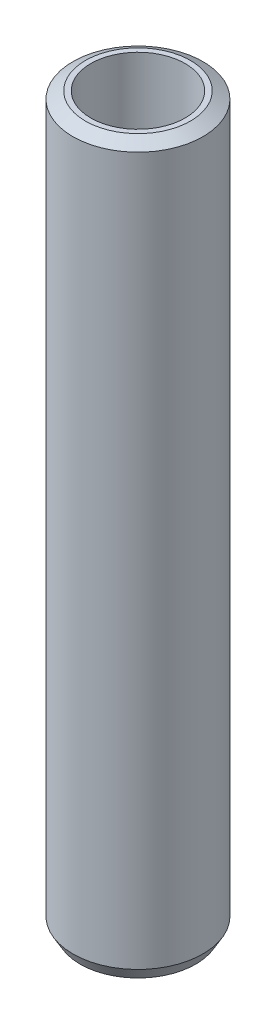
SolidWorks part; units mm, degrees
ref_plane "Front Plane" through (0, 0, 0) normal (0, 0, 1) x (1, 0, 0)
ref_plane "Top Plane" through (0, 0, 0) normal (0, 1, 0) x (1, 0, 0)
ref_plane "Right Plane" through (0, 0, 0) normal (1, 0, 0) x (0, 0, -1)
sketch "Sketch1" plane through (0, 0, 0) normal (0, 1, 0) x (1, 0, 0)
  circle A0 centre (0, 0) radius 50
  dimension "SHAFT_OD" = 100
extrude "Boss-Extrude1" add sketch "Sketch1" along normal blind 559.1242
sketch "Sketch2" plane through (0, 0, 0) normal (0, 1, 0) x (1, 0, 0)
  circle A0 centre (0, 0) radius 36.2845
  dimension "BORE_D" = 72.5689
extrude "Cut-Extrude1" cut sketch "Sketch2" along normal through all
chamfer "Chamfer1" distance 5.5601 angle 60 2 edges at (0, 559.1242, 50) (0, 0, 50) first distance on face at (0, 559.1242, 50) first distance on face at (0, 0, 36.2845)
